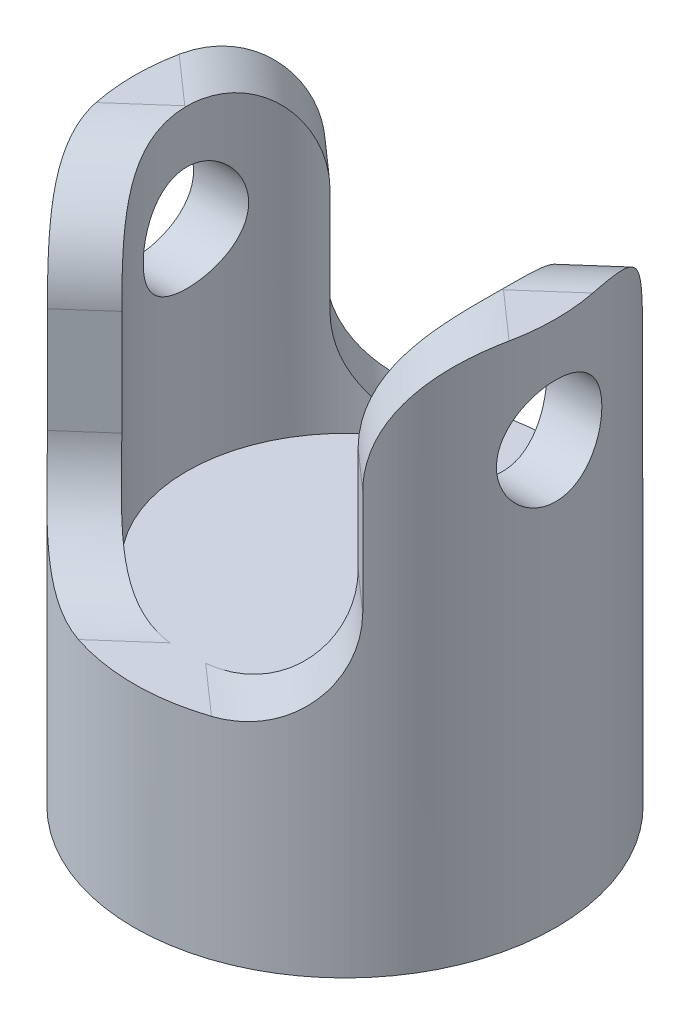
SolidWorks part; units mm, degrees
ref_plane "Front Plane" through (0, 0, 0) normal (0, 0, 1) x (1, 0, 0)
ref_plane "Top Plane" through (0, 0, 0) normal (0, 1, 0) x (1, 0, 0)
ref_plane "Right Plane" through (0, 0, 0) normal (1, 0, 0) x (0, 0, -1)
sketch "Sketch1" plane through (0, 0, 0) normal (0, 1, 0) x (1, 0, 0)
  circle A0 centre (0, 0) radius 5 construction
  circle A1 centre (0, 0) radius 6
  dimension "D1" = 10
  dimension "D2" = 1
extrude "Boss-Extrude1" add sketch "Sketch1" along normal blind 6
sketch "Sketch3" plane through (0, 6, 0) normal (0, 1, 0) x (1, 0, 0)
  line L0 (4.4442, -4.0311) -> (4.4879, -3.9823)
  line L3 (-4.512, 3.9549) -> (-3.387, 2.9628)
  line L4 (3.3629, -2.9901) -> (4.4879, -3.9823)
  line L5 (-4.4879, -3.9823) -> (-3.3629, -2.9901)
  line L6 (4.512, 3.9549) -> (3.387, 2.9628)
  arc A0 (4.4442, -4.0311) -> (4.512, 3.9549) centre (0, 0) ccw
  arc A1 (-3.387, 2.9628) -> (-3.3629, -2.9901) centre (0, 0) ccw
  arc A2 (3.3629, -2.9901) -> (3.387, 2.9628) centre (0, 0) ccw
  arc A3 (-4.512, 3.9549) -> (-4.4879, -3.9823) centre (0, 0) ccw
  point P12 (0, 0)
  circle M4 centre (0, 0) radius 6
  dimension "D1" = 1.5
  dimension "D2" = 12
extrude "Boss-Extrude2" add sketch "Sketch3" along normal blind 9 contours A1 L3 L5 M4 | A2 L4 L6 M4 region at (4.8374, 6, 0.0167) region at (-4.8374, 6, 0.0167)
fillet "Fillet1" radius 3 4 edges at (3.9254, 15, 3.4862) (3.9495, 15, -3.4589) (-3.9495, 15, -3.4589) (-3.9254, 15, 3.4862)
fillet "Fillet2" radius 3 4 edges at (3.9495, 6, -3.4589) (-3.9495, 6, -3.4589) (3.9254, 6, 3.4862) (-3.9254, 6, 3.4862)
sketch "Sketch4" plane through (0, 0, 0) normal (1, 0, 0) x (0, 0, -1)
  circle A0 centre (0, 12) radius 1.5
  point P2 (0, 0)
  dimension "D1" = 3
  dimension "D2" = 12
extrude "Cut-Extrude2" cut sketch "Sketch4" against normal through all both and the other way through all
sketch "Sketch5" plane through (0, 0, 0) normal (0, -1, 0) x (1, 0, 0)
  circle A0 centre (0, 0) radius 5
  circle A1 centre (0, 0) radius 6 construction
  dimension "D1" = 1
extrude "Cut-Extrude3" cut sketch "Sketch5" against normal blind 4
